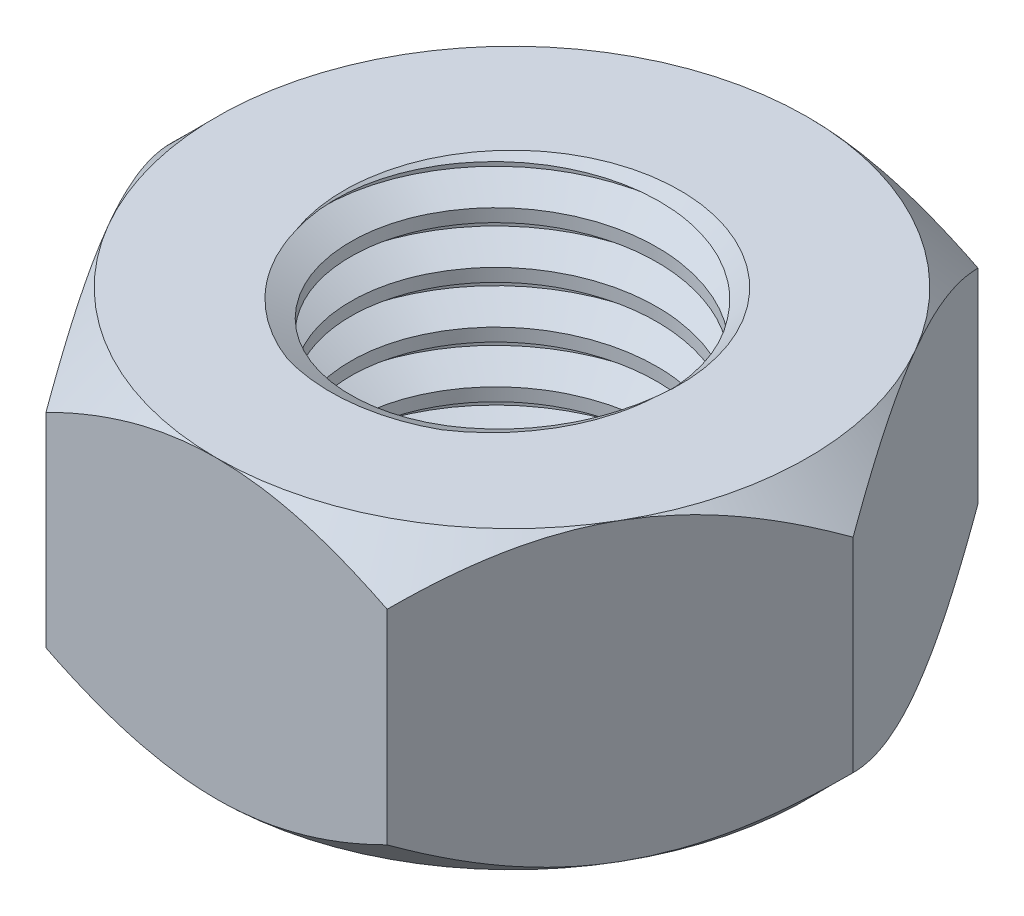
SolidWorks part; units mm, degrees
ref_plane "Front Plane" through (0, 0, 0) normal (0, 0, 1) x (1, 0, 0)
ref_plane "Top Plane" through (0, 0, 0) normal (0, 1, 0) x (1, 0, 0)
ref_plane "Right Plane" through (0, 0, 0) normal (1, 0, 0) x (0, 0, -1)
sketch "Sketch1" plane through (0, 0, 0) normal (0, 1, 0) x (1, 0, 0)
  line L1 (11.547, 0) -> (5.7735, 10)
  line L2 (5.7735, 10) -> (-5.7735, 10)
  line L3 (-5.7735, 10) -> (-11.547, 0)
  line L4 (-11.547, 0) -> (-5.7735, -10)
  line L5 (-5.7735, -10) -> (5.7735, -10)
  line L6 (5.7735, -10) -> (11.547, 0)
  circle A0 centre (0, 0) radius 10 construction
  dimension "D1" = 20
extrude "Boss-Extrude4" add sketch "Sketch1" along normal mid plane 10
sketch "Sketch4" plane through (0, 5, 0) normal (0, 1, 0) x (1, 0, 0)
  line L3 (-5.7735, -10) -> (5.7735, -10) construction
  circle A0 centre (0, 0) radius 10
extrude "Cut-Extrude2" cut sketch "Sketch4" against normal blind 10 draft 45 flip side to cut
mirror "Mirror2" about plane through (0, 0, 0) normal (0, 1, 0) of "Cut-Extrude2"
sketch "Sketch5" plane through (0, 5, 0) normal (0, 1, 0) x (1, 0, 0)
  circle A0 centre (0, 0) radius 5.19
  dimension "D1" = 10.38
extrude "Cut-Extrude3" cut sketch "Sketch5" against normal blind 10
chamfer "Chamfer1" distance 0.5 angle 45 2 edges at (0, -5, 5.19) (0, 5, 5.19)
thread "Thread1" pitch 1.75 start angle 0, offset 3, length 0, pitch 1.75, diameter 10.38
ref_plane "Plane1" through (5.19, -7.5, 0) normal (0, 0, 1) x (1, 0, 0)
sketch "Thread Profile1" plane through (5.19, -7.5, 0) normal (0, 0, 1) x (1, 0, 0)
  line L0 (0, 0) -> (0, 1.75) construction
  line L1 (0, 0) -> (0.9472, 0.5469)
  line L2 (0.9472, 0.5469) -> (0.9472, 0.7656)
  line L3 (0.9472, 0.7656) -> (0, 1.3125)
  line L4 (0.9472, 0.6562) -> (0, 0.6562) construction
  line L11 (0, 0) -> (0, 1.3125)
  point P2 (0, 0)
  dimension "Pitch" = 1.75
  dimension "Profile_Angle" = 60
  dimension "Profile_Land" = 0.2188
  dimension "Profile_Height" = 0.9472
